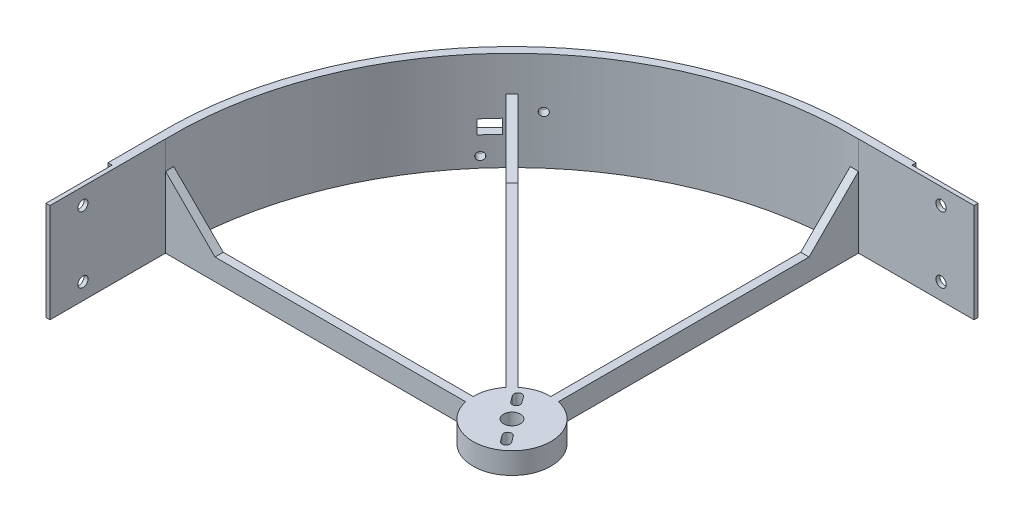
SolidWorks part; units mm, degrees
material "ABS"
ref_plane "Front Plane" through (0, 0, 0) normal (0, 0, 1) x (1, 0, 0)
ref_plane "Top Plane" through (0, 0, 0) normal (0, 1, 0) x (1, 0, 0)
ref_plane "Right Plane" through (0, 0, 0) normal (1, 0, 0) x (0, 0, -1)
sketch "Sketch1" plane through (0, 0, 0) normal (0, 1, 0) x (1, 0, 0)
  line L0 (0, 130.175) -> (0, 9.3426)
  line L1 (3.175, 9.3426) -> (3.175, 130.1363)
  line L2 (0, 0) -> (-22.0351, 22.0351) construction
  line L3 (-22.0351, 22.0351) -> (23.6345, -23.6345) construction
  line L4 (-9.3426, -3.175) -> (-130.1363, -3.175)
  line L5 (-130.175, 0) -> (-9.3426, 0)
  line L6 (3.175, 9.3426) -> (3.175, 130.1363)
  line L7 (3.175, 130.1363) -> (3.175, 133.3122)
  line L8 (-130.1363, -3.175) -> (-133.3122, -3.175)
  line L9 (-93.1633, 90.9182) -> (-10.2883, 8.0432)
  line L10 (-90.9182, 93.1633) -> (-7.1863, 9.4313)
  line L11 (0, 0) -> (-130.175, 0)
  line L12 (-130.175, 0) -> (-129.9364, 0.0546) construction
  line L13 (0, 0) -> (0, 146.05) construction
  circle A0 centre (0, 0) radius 15
  arc A1 (3.175, 130.1363) -> (-130.1363, -3.175) centre (0, 0) ccw
  arc A2 (3.175, 133.3122) -> (-133.3122, -3.175) centre (0, 0) ccw
  point P22 (0, 0)
  dimension "D1" = 30
  dimension "D2" = 133.35
  dimension "D4" = 3.175
  dimension "D3" = 3.175
  dimension "D6" = 1.5875
  dimension "D5" = 1.5875
extrude "Boss-Extrude2" add sketch "Sketch1" along normal blind 8.255 contours A0
extrude "Boss-Extrude3" add sketch "Sketch1<6>" along normal blind 8.255 contours L5 A1 L4 A0 | L6 A1 L0 A0 | A1 A0 region at (1.5882, 0, -72.5246) region at (-51.3161, 0, -51.3161) region at (-72.5246, 0, 1.5882)
sketch "Sketch1<6>" plane through (0, 0, 0) normal (0, 1, 0) x (1, 0, 0) same geometry as "Sketch1"
extrude "Boss-Extrude4" add sketch "Sketch1<7>" along normal blind 38.1 contours L7 A2 L8 A1 region at (-49.8095, 0, -122.3558)
sketch "Sketch1<7>" plane through (0, 0, 0) normal (0, 1, 0) x (1, 0, 0) same geometry as "Sketch1"
ref_plane "Plane1" through (-63.4806, 0, -63.4806) normal (0.7071, 0, 0.7071) x (0.7071, 0, -0.7071)
sketch "Sketch5" plane through (0, 8.255, 0) normal (0, 1, 0) x (1, 0, 0)
  line L0 (0, 0) -> (29.635, 0) construction
  line L1 (0, 0) -> (0, 21.5427) construction
  line L2 (0, 130.175) -> (0, 15) construction
  line L3 (0, 0) -> (29.1655, -1.7838) construction
  line L4 (21.3209, -1.304) -> (-27.7157, 1.6952) construction
  line L5 (0, 0) -> (1.3244, 21.6543) construction
  line L6 (0, 8) -> (0, 0) construction
  line L7 (0, 0) -> (37.8993, -60.1598) construction
  line L8 (0, 0) -> (-19.6346, 0) construction
  line L9 (-130.175, 0) -> (-15, 0) construction
  circle A6 centre (0, 0) radius 3.25
  point P18 (0, 0)
  dimension "D8" = 6.5
  dimension "D2" = 8
  dimension "D5" = 93.5
  dimension "D9" = 90
  dimension "D4" = 57.79
extrude "Cut-Extrude3" cut sketch "Sketch5" against normal blind 63.5
sketch "Sketch6" plane through (0, 0, 3.175) normal (0, 0, 1) x (1, 0, 0)
  line L0 (-14.6601, 0) -> (-133.3122, 0) construction
  line L1 (-130.1363, 38.1) -> (-131.7242, 38.1)
  line L2 (-130.1363, 38.1) -> (-130.1363, 0)
  line L3 (-130.1363, 0) -> (-131.7242, 0)
  line L4 (-131.7242, 38.1) -> (-131.7242, 0)
  line L5 (-130.1363, 38.1) -> (-133.3122, 38.1) construction
  point P7 (-131.7242, 38.1)
sketch "Sketch7" plane through (3.175, 0, 0) normal (1, 0, 0) x (0, 0, -1)
  line L0 (14.6601, 0) -> (133.3122, 0) construction
  line L1 (130.1363, 38.1) -> (131.7242, 38.1)
  line L2 (130.1363, 38.1) -> (130.1363, 0)
  line L3 (130.1363, 0) -> (131.7242, 0)
  line L4 (131.7242, 38.1) -> (131.7242, 0)
  line L5 (130.1363, 38.1) -> (133.3122, 38.1) construction
  line L6 (130.1363, 38.1) -> (130.1363, 8.255) construction
  point P7 (131.7242, 38.1)
ref_plane "Plane3" through (1.1225, 0, -1.1225) normal (0.7071, 0, -0.7071) x (-0.7071, 0, -0.7071)
ref_plane "Plane5" through (0, 0, 0) normal (0, 0, -1) x (-1, 0, 0)
sketch "Sketch14" plane through (0, 0, 0) normal (0, 0, -1) x (-1, 0, 0)
  line L0 (130.175, 8.255) -> (111.125, 8.255)
  line L2 (130.175, 8.255) -> (15, 8.255) construction
  line L5 (130.175, 8.255) -> (130.175, 27.305)
  line L6 (130.175, 8.255) -> (130.175, 38.1) construction
  line L7 (130.175, 27.305) -> (111.125, 8.255)
  dimension "D1" = 19.05
  dimension "D2" = 45
extrude "Boss-Extrude13" add sketch "Sketch14" against normal blind 3.175
ref_plane "Plane6" through (0, 0, 0) normal (-1, 0, 0) x (0, 0, 1)
sketch "Sketch15" plane through (0, 0, 0) normal (-1, 0, 0) x (0, 0, 1)
  line L0 (-130.175, 8.255) -> (-130.175, 27.305)
  line L1 (-130.175, 38.1) -> (-130.175, 8.255) construction
  line L2 (-130.175, 27.305) -> (-111.125, 8.255)
  line L3 (-130.175, 8.255) -> (-15, 8.255) construction
  line L5 (-111.125, 8.255) -> (-130.175, 8.255)
  dimension "D1" = 19.05
  dimension "D2" = 45
extrude "Boss-Extrude14" add sketch "Sketch15" against normal blind 3.175
sketch "Sketch16" plane through (1.1225, 0, -1.1225) normal (0.7071, 0, -0.7071) x (-0.7071, 0, -0.7071)
  line L0 (133.3403, 8.255) -> (111.1153, 8.255)
  line L2 (130.1653, 8.255) -> (14.9158, 8.255) construction
  line L4 (133.3403, 8.255) -> (133.3403, 27.305)
  line L5 (133.3403, 27.305) -> (111.1153, 8.255)
  dimension "D1" = 22.225
  dimension "D2" = 19.05
extrude "Boss-Extrude15" add sketch "Sketch16" against normal blind 3.175
sketch "Sketch17" plane through (0, 8.255, 0) normal (0, 1, 0) x (1, 0, 0)
  line L0 (3.9871, -3.9871) -> (-70.6135, 70.6135) construction
  line L1 (-4.6836, 6.3296) -> (-6.4967, 8.7797) construction
  line L2 (-5.9087, 5.4231) -> (-7.7217, 7.8732)
  line L3 (-3.4586, 7.2361) -> (-5.2716, 9.6862)
  line L4 (0, 0) -> (18.699, 19.3885) construction
  line L5 (-6.4967, 8.7797) -> (0, 0) construction
  line L6 (0, 0) -> (4.11, 3.0412) construction
  line L7 (4.6836, -6.3296) -> (6.4967, -8.7797) construction
  line L8 (3.4586, -7.2361) -> (5.2716, -9.6862)
  line L9 (5.9087, -5.4231) -> (7.7217, -7.8732)
  line L12 (-79.6929, 77.4479) -> (-11.6696, 9.4245) construction
  arc A0 (-5.9087, 5.4231) -> (-3.4586, 7.2361) centre (-4.6836, 6.3296) ccw
  arc A1 (-5.2716, 9.6862) -> (-7.7217, 7.8732) centre (-6.4967, 8.7797) ccw
  arc A2 (3.4586, -7.2361) -> (5.9087, -5.4231) centre (4.6836, -6.3296) cw
  arc A3 (7.7217, -7.8732) -> (5.2716, -9.6862) centre (6.4967, -8.7797) cw
  point P3 (-5.5901, 7.5546)
  point P9 (0, 0)
  point P17 (5.5901, -7.5546)
  dimension "D1" = 7.874
  dimension "D2" = 3.048
  dimension "D3" = 3.048
  dimension "D4" = 8.5
extrude "Cut-Extrude6" cut sketch "Sketch17" against normal through all
ref_plane "Plane7" through (0, 0, -131.7242) normal (0, 0, -1) x (0, -1, 0)
sketch "Sketch20" plane through (0, 0, -131.7242) normal (0, 0, -1) x (0, -1, 0)
  line L0 (-38.1, -3.175) -> (-38.1, -47.625)
  line L1 (-38.1, -47.625) -> (0, -47.625)
  line L2 (0, -47.625) -> (0, -3.175)
  line L3 (0, -3.175) -> (-38.1, -3.175)
  dimension "D1" = 44.45
extrude "Boss-Extrude16" add sketch "Sketch20" against normal blind 1.524
ref_plane "Plane8" through (-131.7242, 0, 0) normal (-1, 0, 0) x (0, -1, 0)
sketch "Sketch21" plane through (-131.7242, 0, 0) normal (-1, 0, 0) x (0, -1, 0)
  line L1 (-38.1, 47.625) -> (0, 47.625)
  line L2 (-38.1, 47.625) -> (-38.1, 3.175)
  line L3 (-38.1, 3.175) -> (0, 3.175)
  line L4 (0, 47.625) -> (0, 3.175)
  dimension "D1" = 44.45
extrude "Boss-Extrude17" add sketch "Sketch21" against normal blind 1.524
sketch "Sketch23" plane through (-131.7242, 0, 0) normal (-1, 0, 0) x (0, 0, 1)
  line L1 (-19.05, 19.05) -> (57.15, 19.05) construction
  line L2 (47.625, 38.1) -> (3.175, 38.1) construction
  line L3 (47.625, 0) -> (47.625, 38.1) construction
  circle A0 centre (34.925, 31.75) radius 1.9431
  circle A1 centre (34.925, 6.35) radius 1.9431
  dimension "D2" = 3.8862
  dimension "D1" = 12.7
  dimension "D3" = 19.05
  dimension "D4" = 12.7
extrude "Cut-Extrude7" cut sketch "Sketch23" against normal blind 2.54
sketch "Sketch24" plane through (0, 0, -131.7242) normal (0, 0, -1) x (-1, 0, 0)
  line L1 (-44.45, 19.05) -> (-3.175, 19.05) construction
  line L2 (-3.175, 0) -> (-3.175, 38.1) construction
  line L3 (-47.625, 38.1) -> (-47.625, 0) construction
  circle A0 centre (-34.925, 31.75) radius 1.985
  circle A1 centre (-34.925, 6.35) radius 1.985
  dimension "D2" = 3.97
  dimension "D1" = 12.7
  dimension "D3" = 12.7
extrude "Cut-Extrude8" cut sketch "Sketch24" against normal blind 2.54
sketch "Sketch25" plane through (-131.7242, 0, 0) normal (-1, 0, 0) x (0, 0, 1)
  line L0 (3.175, 0) -> (47.625, 0) construction
  line L1 (3.175, 38.1) -> (22.225, 38.1)
  line L2 (3.175, 38.1) -> (3.175, 0)
  line L3 (3.175, 0) -> (22.225, 0)
  line L4 (22.225, 38.1) -> (22.225, 0)
  dimension "D1" = 19.05
extrude "Boss-Extrude18" add sketch "Sketch25" along normal up to vertex (1.588 mm away) up to point (-133.3122, 0, 3.175)
sketch "Sketch26" plane through (0, 0, -131.7242) normal (0, 0, -1) x (-1, 0, 0)
  line L0 (-47.625, 0) -> (-3.175, 0) construction
  line L1 (-3.175, 38.1) -> (-22.225, 38.1)
  line L2 (-3.175, 38.1) -> (-3.175, 0)
  line L3 (-3.175, 0) -> (-22.225, 0)
  line L4 (-22.225, 38.1) -> (-22.225, 0)
  dimension "D1" = 19.05
extrude "Boss-Extrude19" add sketch "Sketch26" along normal up to vertex (1.588 mm away) up to point (3.175, 0, -133.3122)
ref_plane "Plane9" through (-94.2927, 0, -94.2927) normal (-0.7071, 0, -0.7071) x (-0.7071, 0, 0.7071)
sketch "Sketch27" plane through (-94.2927, 0, -94.2927) normal (-0.7071, 0, -0.7071) x (-0.7071, 0, 0.7071)
  line L0 (0, 0) -> (0, 28.4929) construction
  line L1 (-12.7, 0) -> (12.7, 0)
  line L2 (12.7, 0) -> (12.7, 22.8113)
  line L3 (12.7, 22.8113) -> (-12.7, 22.8113)
  line L4 (-12.7, 0) -> (-12.7, 22.8113)
  point P8 (0, 22.8113)
extrude "Boss-Extrude20" add sketch "Sketch27" against normal up to surface (0.6061 mm away) up to face at (-79.6806, 19.05, -79.6806)
sketch "Sketch29" plane through (-94.2927, 0, -94.2927) normal (-0.7071, 0, -0.7071) x (-0.7071, 0, 0.7071)
  line L0 (-12.7, 0) -> (12.7, 0) construction
  line L2 (12.7, 0) -> (12.7, 22.8113) construction
  line L3 (-12.7, 0) -> (12.7, 22.8113) construction
  line L4 (12.7, 22.8113) -> (0, 22.8113) construction
  line L5 (12.7, 0) -> (12.7, 22.8113) construction
  line L6 (-12.7, 22.8113) -> (-12.7, 0) construction
  line L7 (0, 22.8113) -> (-12.7, 22.8113) construction
  circle A0 centre (8.636, 4.064) radius 1.524
  circle A1 centre (-8.636, 18.7473) radius 1.524
  dimension "D1" = 4.064
  dimension "D5" = 3.048
  dimension "D6" = 3.048
  dimension "D2" = 4.064
  dimension "D3" = 4.064
  dimension "D4" = 4.064
extrude "Cut-Extrude9" cut sketch "Sketch29" against normal up to surface (3.5721 mm away) up to face at (-76.9617, 19.5448, -76.9617)
sketch "Sketch30" plane through (-94.2927, 0, -94.2927) normal (-0.7071, 0, -0.7071) x (-0.7071, 0, 0.7071)
  line L0 (12.7, 22.8113) -> (0, 22.8113) construction
  line L1 (2.5707, 16.4613) -> (9.525, 16.4613)
  line L2 (2.5707, 16.4613) -> (2.5707, 11.1121)
  line L3 (2.5707, 11.1121) -> (9.525, 11.1121)
  line L4 (9.525, 16.4613) -> (9.525, 11.1121)
  line L5 (12.7, 0) -> (12.7, 22.8113) construction
  dimension "D1" = 6.35
  dimension "D2" = 3.175
extrude "Cut-Extrude10" cut sketch "Sketch30" against normal up to surface (3.5239 mm away) up to face at (-84.6138, 18.3969, -98.9244)
